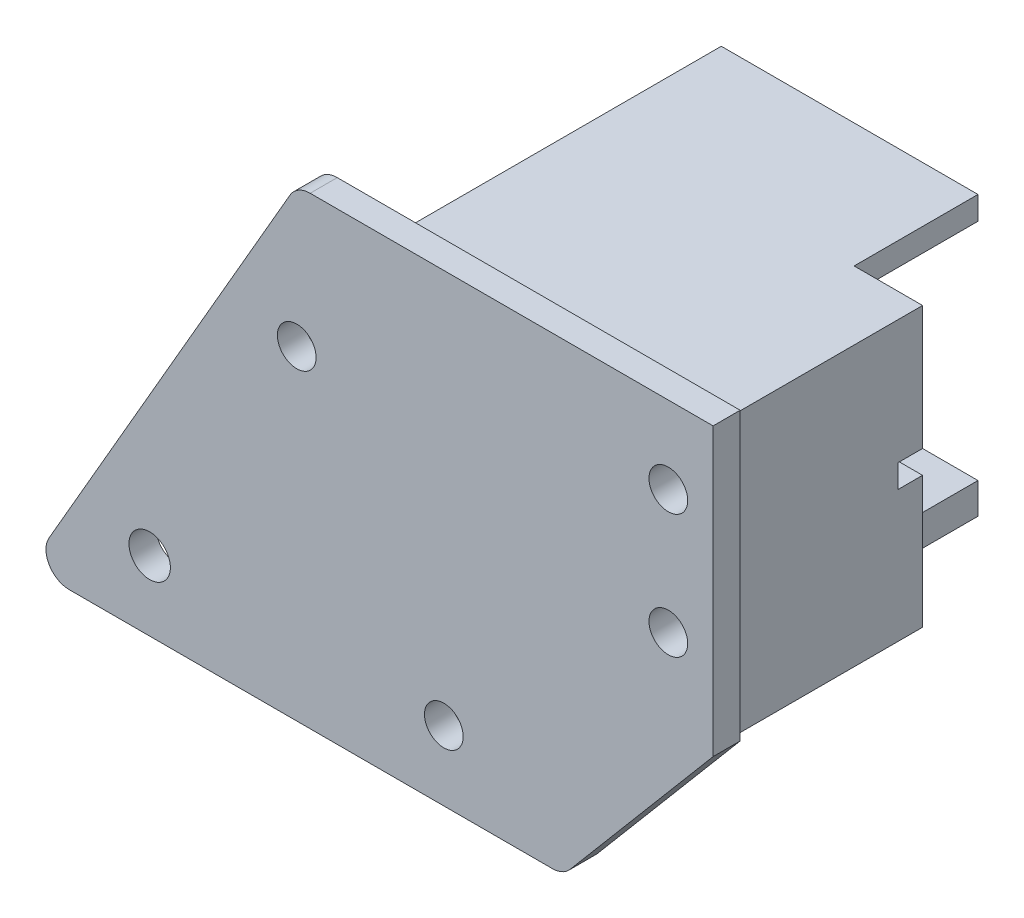
SolidWorks part; units mm, degrees
note: The reader was unsure of these and kept them because the rebuilt part matched: shared geometry of "Sketch2<4>", "Sketch2<7>", "Sketch2<9>", "Sketch2<10>", "Sketch2<11>".
ref_plane "Front Plane" through (0, 0, 0) normal (0, 0, 1) x (1, 0, 0)
ref_plane "Top Plane" through (0, 0, 0) normal (0, 1, 0) x (1, 0, 0)
ref_plane "Right Plane" through (0, 0, 0) normal (1, 0, 0) x (0, 0, -1)
sketch "Sketch1" plane through (0, 0, 0) normal (0, 0, 1) x (1, 0, 0)
  line L0 (-32.7569, -9) -> (36.2431, -9)
  line L1 (36.2431, -9) -> (55.6126, 13.909)
  line L2 (1.8315, 50.909) -> (-32.7569, -9)
  line L3 (55.6126, 13.909) -> (55.6126, 50.909)
  line L4 (55.6126, 50.909) -> (1.8315, 50.909)
  circle A0 centre (-17.1685, 0) radius 2.675
  circle A1 centre (20.8315, 0) radius 2.5
  circle A2 centre (1.8315, 32.909) radius 2.5
  dimension "D5" = 5.35
  dimension "D7" = 5
  dimension "D8" = 5
  dimension "D1" = 38
  dimension "D2" = 38
  dimension "D3" = 38
  dimension "D4" = 9
  dimension "D6" = 9
  dimension "D9" = 69
  dimension "D10" = 30
  dimension "D11" = 37
  dimension "D12" = 69.1769
  dimension "D13" = 53.7811
extrude "Boss-Extrude1" add sketch "Sketch1" along normal blind 3.5
fillet "Fillet1" radius 3 3 edges at (-32.7569, -9, 1.75) (1.8315, 50.909, 1.75) (36.2431, -9, 1.75)
sketch "Sketch2" plane through (0, 0, 0) normal (0, 0, -1) x (-1, 0, 0)
  line L0 (-55.1719, 32.909) -> (20.3281, 32.909) construction
  line L1 (-55.1719, 47.409) -> (20.3281, 47.409)
  line L2 (-55.1719, 47.409) -> (-55.1719, 18.409)
  line L3 (-55.1719, 18.409) -> (20.3281, 18.409)
  line L4 (20.3281, 47.409) -> (20.3281, 18.409)
  line L5 (-55.1719, 47.409) -> (20.3281, 18.409) construction
  line L6 (-55.1719, 18.409) -> (20.3281, 47.409) construction
  line L7 (-46.3315, 47.409) -> (-46.3315, 18.409)
  line L8 (12.1685, 47.409) -> (12.1685, 18.409)
  line L9 (16.1685, 47.409) -> (16.1685, 18.409) construction
  line L10 (-49.8315, 47.409) -> (-49.8315, 18.409) construction
  line L11 (12.1685, 34.409) -> (20.3281, 34.409)
  line L12 (20.3281, 34.409) -> (20.3281, 31.409)
  line L13 (20.3281, 31.409) -> (12.1685, 31.409)
  line L14 (-46.3315, 34.409) -> (-55.1719, 34.409)
  line L15 (-46.3315, 31.409) -> (-55.1719, 31.409)
  line L16 (-46.3315, 47.409) -> (12.1685, 18.409) construction
  line L17 (12.1685, 18.409) -> (12.1685, 47.409) construction
  line L18 (12.1685, 47.409) -> (-46.3315, 18.409) construction
  line L19 (-13.1719, 47.409) -> (-13.1719, 18.409)
  line L20 (-55.1719, 47.409) -> (-13.1719, 47.409)
  line L21 (-55.1719, 47.409) -> (-55.1719, 50.409)
  line L22 (-55.1719, 50.409) -> (-13.1719, 50.409)
  line L23 (-13.1719, 47.409) -> (-13.1719, 50.409)
  line L24 (-55.1719, 18.409) -> (16.1685, 18.409)
  line L25 (-55.1719, 18.409) -> (11.923, 18.409)
  line L26 (-55.1719, 18.409) -> (-55.1719, 14.409)
  line L27 (-55.1719, 14.409) -> (11.923, 14.409)
  line L28 (11.923, 18.409) -> (11.923, 14.409)
  line L30 (-55.1719, 50.409) -> (-46.3315, 50.409)
  line L31 (-55.1719, 50.409) -> (-55.1719, 14.409)
  line L32 (-55.1719, 14.409) -> (-46.3315, 14.409)
  line L33 (-46.3315, 50.409) -> (-46.3315, 14.409)
  circle A0 centre (-1.8315, 32.909) radius 4.125
  circle A1 centre (16.1685, 40.909) radius 2.5
  circle A2 centre (16.1685, 24.909) radius 2.5
  circle A3 centre (-49.8315, 24.909) radius 2.5
  circle A4 centre (-49.8315, 40.909) radius 2.5
  point P0 (-17.4219, 32.909)
  point P26 (-17.0815, 32.909)
  dimension "D2" = 8.25
  dimension "D12" = 5
  dimension "D1" = 75.5
  dimension "D3" = 14
  dimension "D4" = 44.5
  dimension "D5" = 66
  dimension "D6" = 3
  dimension "D7" = 1.5
  dimension "D8" = 3
  dimension "D9" = 4
  dimension "D10" = 3.5
  dimension "D11" = 58.5
  dimension "D13" = 16
  dimension "D14" = 16
  dimension "D15" = 8
  dimension "D16" = 8
  dimension "D17" = 29
  dimension "D18" = 3
  dimension "D19" = 4
  dimension "D20" = 42
extrude "Boss-Extrude2" add sketch "Sketch2" against normal blind 3.5 contours A4 | A3 | A2 | A1 | L1 L4 L3 L2 | A0
extrude "Boss-Extrude3" add sketch "Sketch2<4>" along direction (0, 0, -1) on the side of the normal blind 24 from surface at 0 contours L3 L33 L27 L28 | L33 L3 L26 L27 | L7 L15 L2 L3 A3 | L14 L7 L1 L2 A4 | L33 L22 L21 L1 | L22 L33 L1 L23
sketch "Sketch2<4>" plane through (0, 0, 0) normal (0, 0, -1) x (-1, 0, 0) same geometry as "Sketch2"
fillet "Fillet2" radius 3 1 edges at (-16.9324, 18.409, 1.75)
fillet "Fillet3" [suppressed] radius 3
extrude "Boss-Extrude5" add sketch "Sketch2<7>" along a picked direction on the side of the normal offset from surface (20.8 mm away) 3.2 contours L15 L7 L14 L2
sketch "Sketch2<7>" plane through (0, 0, 0) normal (0, 0, -1) x (-1, 0, 0) same geometry as "Sketch2"
sketch "Sketch3" plane through (0, 0, 0) normal (0, 0, -1) x (-1, 0, 0)
  line L0 (-1.8315, 50.909) -> (32.7569, -9) construction
  line L1 (-1.8315, 50.909) -> (32.7569, -9)
  line L2 (32.7569, -9) -> (32.7569, 50.909)
  line L3 (32.7569, 50.909) -> (-1.8315, 50.909)
extrude "Cut-Extrude3" cut sketch "Sketch2<9>" against normal through all contours A4 | A3
sketch "Sketch2<9>" plane through (0, 0, 0) normal (0, 0, -1) x (-1, 0, 0) same geometry as "Sketch2"
extrude "Cut-Extrude1" cut sketch "Sketch3" against normal through all
extrude "Boss-Extrude6" add sketch "Sketch2<10>" along normal blind 40 contours L1 L23 L22 L21 | L28 L3 L26 L27
sketch "Sketch2<10>" plane through (0, 0, 0) normal (0, 0, -1) x (-1, 0, 0) same geometry as "Sketch2"
extrude "Boss-Extrude7" add sketch "Sketch2<11>" along normal offset from surface (15.25 mm away) 8.75 contours L19 L1 L7 L3 up to face at (47.3315, 40.909, -24)
sketch "Sketch2<11>" plane through (0, 0, 0) normal (0, 0, -1) x (-1, 0, 0) same geometry as "Sketch2"
equation "\"D2@Sketch1\"=\"D1@Sketch1\""
equation "\"D3@Sketch1\"=\"D1@Sketch1\""
equation "\"D6@Sketch1\"=\"D4@Sketch1\""
equation "\"D7@Sketch2\"=\"D6@Sketch2\"/2"
equation "\"D8@Sketch2\"=3"
